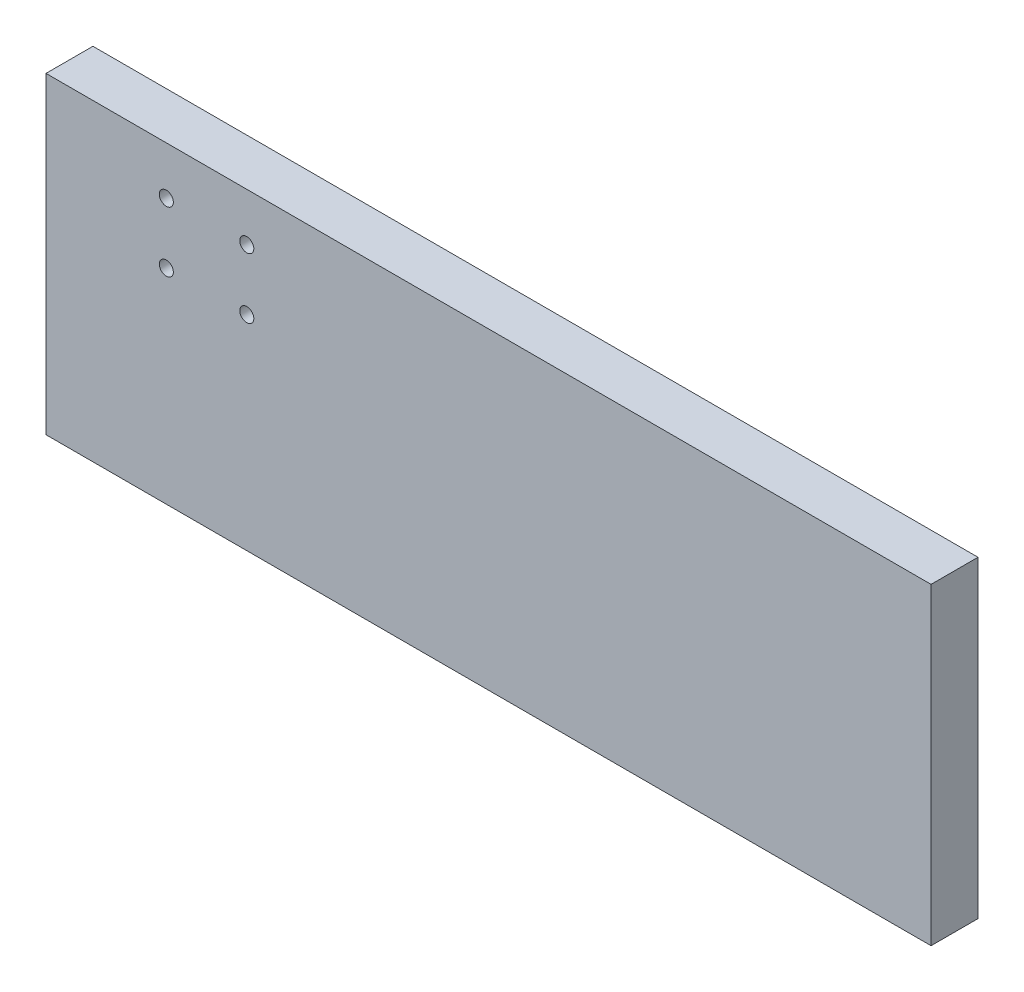
SolidWorks part; units mm, degrees
ref_plane "Front Plane" through (0, 0, 0) normal (0, 0, 1) x (1, 0, 0)
ref_plane "Top Plane" through (0, 0, 0) normal (0, 1, 0) x (1, 0, 0)
ref_plane "Right Plane" through (0, 0, 0) normal (1, 0, 0) x (0, 0, -1)
sketch "Sketch1" plane through (0, 0, 0) normal (0, 0, 1) x (1, 0, 0)
  line L1 (0, 0) -> (359.156, 0)
  line L2 (0, 0) -> (0, 127)
  line L3 (0, 127) -> (359.156, 127)
  line L4 (359.156, 0) -> (359.156, 127)
  dimension "D1" = 127
  dimension "D2" = 359.156
extrude "Boss-Extrude1" add sketch "Sketch1" along normal blind 19.05
sketch "Sketch2" plane through (0, 0, 19.05) normal (0, 0, 1) x (1, 0, 0)
  circle A0 centre (48.8251, 82.9627) radius 2.8511
  circle A1 centre (48.8251, 107.5372) radius 2.8511
  circle A2 centre (81.4768, 107.5372) radius 2.8512
  circle A3 centre (81.4768, 82.9627) radius 2.8512
extrude "Cut-Extrude1" cut sketch "Sketch2" against normal up to next
